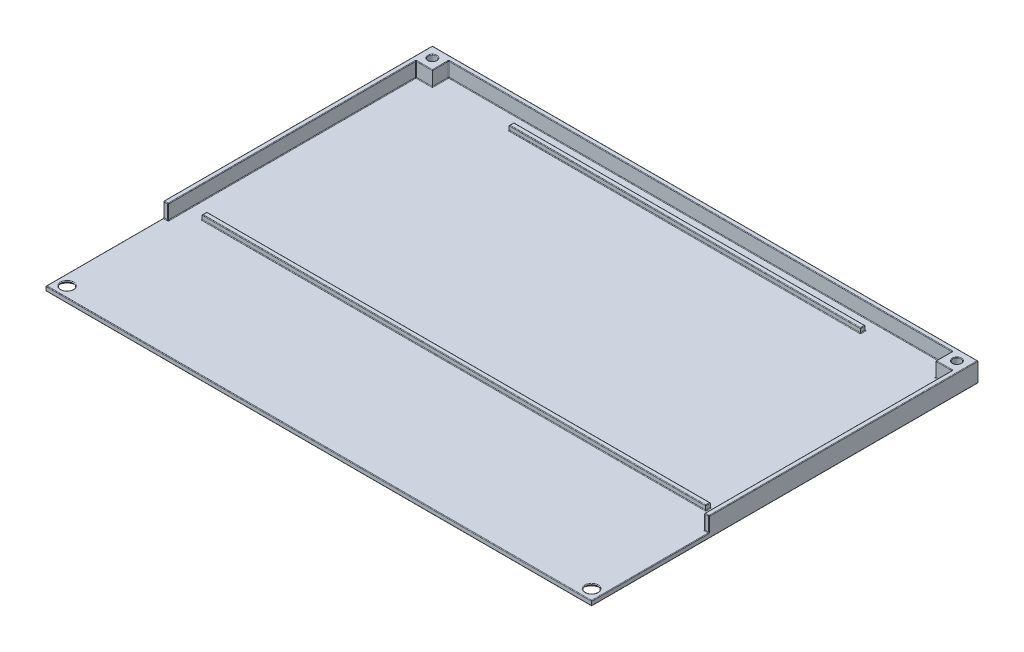
SolidWorks part; units mm, degrees
ref_plane "Front Plane" through (0, 0, 0) normal (0, 0, 1) x (1, 0, 0)
ref_plane "Top Plane" through (0, 0, 0) normal (0, 1, 0) x (1, 0, 0)
ref_plane "Right Plane" through (0, 0, 0) normal (1, 0, 0) x (0, 0, -1)
sketch "Sketch1" plane through (0, 0, 0) normal (0, 1, 0) x (1, 0, 0)
  line L0 (-116.5, 48) -> (-107.5, 48)
  line L1 (107.5, -48) -> (-107.5, -48) construction
  line L2 (107.5, -48) -> (107.5, 48) construction
  line L3 (107.5, 48) -> (-107.5, 48) construction
  line L4 (-107.5, -48) -> (-107.5, 48) construction
  line L5 (107.5, -48) -> (-107.5, 48) construction
  line L6 (107.5, 48) -> (-107.5, -48) construction
  line L7 (-116.5, 57) -> (116.5, 57)
  line L8 (-116.5, 57) -> (-116.5, -108)
  line L9 (-116.5, -108) -> (116.5, -108)
  line L10 (116.5, 57) -> (116.5, -108)
  line L11 (-107.5, 48) -> (-107.5, 57)
  line L12 (-116.5, -99) -> (-107.5, -99)
  line L13 (-107.5, -99) -> (-107.5, -108)
  line L14 (107.5, -108) -> (107.5, -99)
  line L15 (107.5, -99) -> (116.5, -99)
  line L16 (116.5, 48) -> (107.5, 48)
  line L17 (107.5, 48) -> (107.5, 57)
  line L18 (0, -48) -> (0, -108) construction
  line L19 (-107.5, 48) -> (-116.5, 57) construction
  line L20 (107.5, 48) -> (116.5, 57) construction
  line L21 (-107.5, -99) -> (-116.5, -108) construction
  line L22 (107.5, -99) -> (116.5, -108) construction
  line L23 (-107.5, -48) -> (-107.5, -48.3)
  line L24 (107.5, -48) -> (107.5, -48.3) construction
  line L25 (0, 48.3) -> (0, 48) construction
  line L26 (-107.5, -48.3) -> (107.5, -48.3)
  line L27 (-107.5, -48.3) -> (-107.5, -50.3)
  line L28 (-107.5, -50.3) -> (107.5, -50.3)
  line L29 (107.5, -48.3) -> (107.5, -50.3)
  line L30 (-75, 50.3) -> (75, 50.3)
  line L31 (-75, 50.3) -> (-75, 48.3)
  line L32 (-75, 48.3) -> (75, 48.3)
  line L33 (75, 50.3) -> (75, 48.3)
  line L34 (114.5, -57.85) -> (114.5, 48)
  line L35 (-116.5, -108) -> (116.5, -108) construction
  line L36 (-116.5, -108) -> (-116.5, -58) construction
  line L37 (-116.5, -58) -> (116.5, -58) construction
  line L38 (116.5, -108) -> (116.5, -58) construction
  line L39 (107.5, 55) -> (-107.5, 55)
  line L40 (-114.5, 48) -> (-114.5, -57.85)
  line L41 (-116.5, -57.85) -> (116.5, -57.85)
  circle A0 centre (-112, 52.5) radius 1.75
  circle A1 centre (112, 52.5) radius 1.75
  circle A2 centre (112, -103.5) radius 1.75
  circle A3 centre (-112, -103.5) radius 1.75
  point P0 (0, 0)
  point P48 (0, 0)
  point P51 (114.5, -56.3966)
  point P52 (0, 0)
  point P53 (-114.5, -56.3966)
  dimension "D1" = 9
  dimension "D3" = 3.5
  dimension "D5" = 2
  dimension "D2" = 60
  dimension "D4" = 0.3
  dimension "D6" = 215
  dimension "D7" = 96
  dimension "D8" = 2
  dimension "D9" = 150
  dimension "D10" = 0.3
  dimension "D11" = 50
  dimension "D12" = 2
  dimension "D13" = 2
  dimension "D14" = 2
  dimension "D15" = 0.3
extrude "Boss-Extrude1" add sketch "Sketch1" against normal blind 2 contours L16 L17 L7 L11 L0 L8 L12 L13 L9 L14 L15 L10 | L15 L14 L9 L10 A2 | L17 L16 L10 L7 A1 | L13 L12 L8 L9 A3 | L0 L11 L7 L8 A0 | L40 L41 L34 L16 L17 L39 L11 L0 L26 L29 L28 L27 L30 L33 L32 L31 | L34 L41 L10 L16 | L39 L17 L7 L11 | L8 L41 L40 L0 region at (-116.3727, 0, -52.5) region at (-115.5, 0, 4.925) region at (0, 0, 1.4177) region at (0, 0, 82.6357) region at (0, 0, -56) region at (-112, 0, 99.1273) region at (115.5, 0, 4.925) region at (112, 0, -56.8727) region at (116.3727, 0, 103.5)
extrude "Boss-Extrude2" add sketch "Sketch1<3>" along normal mid plane 4 contours L33 L30 L31 L32 | L29 L26 L27 L28 region at (0, 0, 49.3) region at (0, 0, -49.3)
sketch "Sketch1<3>" plane through (0, 0, 0) normal (0, 1, 0) x (1, 0, 0) same geometry as "Sketch1"
extrude "Boss-Extrude3" add sketch "Sketch1<4>" along normal blind 6.3 contours L8 L41 L40 L0 | L34 L41 L10 L16 | L39 L17 L7 L11 | L17 L16 L10 L7 A1 | L0 L11 L7 L8 A0 region at (-116.3727, 0, -52.5) region at (-115.5, 0, 4.925) region at (0, 0, -56) region at (115.5, 0, 4.925) region at (112, 0, -56.8727)
sketch "Sketch1<4>" plane through (0, 0, 0) normal (0, 1, 0) x (1, 0, 0) same geometry as "Sketch1"
chamfer "Chamfer1" distance 2.5 angle 45 4 edges at (112, -2, 105.25) (-112, -2, 105.25) (-112, -2, -50.75) (112, -2, -50.75)
fillet "Fillet1" radius 0.25 60 edges at (0, 2, -48.3) (-75, 2, -49.3) (0, 2, -50.3) (75, 2, -49.3) (0, 2, 50.3) (-107.5, 2, 49.3) (0, 2, 48.3) (107.5, 2, 49.3) (-75, 0, -49.3) (0, 0, -48.3) (75, 0, -49.3) (0, 0, -50.3) (0, 0, 50.3) (107.5, 0, 49.3) (0, 0, 48.3) (-107.5, 0, 49.3) (116.5, 0, 82.925) (0, 0, 108) (-116.5, 0, 82.925) (-112, 0, 105.75) (112, 0, 105.75) (-116.5, -2, 25.5) (0, -2, 108) (116.5, -2, 25.5) (0, -2, -57) (112, -2, -48.25) (-112, -2, -48.25) (-112, -2, 107.75) (112, -2, 107.75) (116.5, 3.15, 57.85) (-116.5, 3.15, 57.85) (-115.5, 0, 57.85) (-114.5, 0, 4.925) (-111, 0, -48) (-107.5, 0, -51.5) (0, 0, -55) (107.5, 0, -51.5) (111, 0, -48) (114.5, 0, 4.925) (115.5, 0, 57.85) (-107.5, 3.15, -55) (107.5, 3.15, -55) (-114.5, 3.15, 57.85) (-114.5, 3.15, -48) (114.5, 3.15, -48) (114.5, 3.15, 57.85) (112, 6.3, -50.75) (-112, 6.3, -50.75) (0, 6.3, -57) (116.5, 6.3, 0.425) (115.5, 6.3, 57.85) (114.5, 6.3, 4.925) (111, 6.3, -48) (107.5, 6.3, -51.5) (0, 6.3, -55) (-107.5, 6.3, -51.5) (-111, 6.3, -48) (-114.5, 6.3, 4.925) (-115.5, 6.3, 57.85) (-116.5, 6.3, 0.425)
